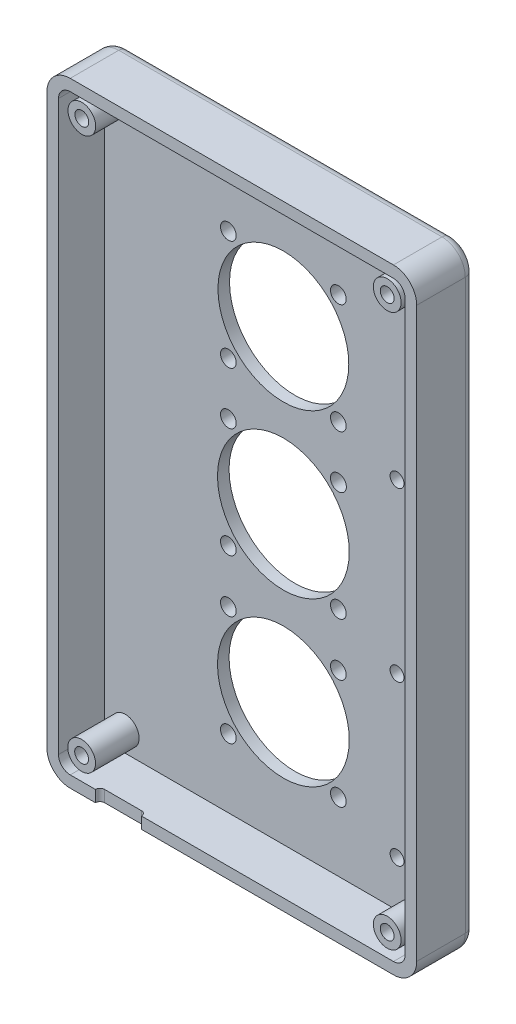
SolidWorks part; units mm, degrees
material "Plastique personnalisé"
ref_plane "Plan de face" through (0, 0, 0) normal (0, 0, 1) x (1, 0, 0)
ref_plane "Plan de dessus" through (0, 0, 0) normal (0, 1, 0) x (1, 0, 0)
ref_plane "Plan de droite" through (0, 0, 0) normal (1, 0, 0) x (0, 0, -1)
sketch "Esquisse1" plane through (0, 0, 0) normal (0, 0, 1) x (1, 0, 0)
  line L1 (-34.96, -64) -> (34.96, -64)
  line L2 (-37.5, -61.46) -> (-37.5, 61.46)
  line L3 (-34.96, 64) -> (34.96, 64)
  line L4 (37.5, -61.46) -> (37.5, 61.46)
  line L5 (-37.5, -64) -> (37.5, 64) construction
  line L6 (-37.5, 64) -> (37.5, -64) construction
  arc A0 (34.96, -64) -> (37.5, -61.46) centre (34.96, -61.46) ccw
  arc A1 (-34.96, -64) -> (-37.5, -61.46) centre (-34.96, -61.46) cw
  arc A2 (-37.5, 61.46) -> (-34.96, 64) centre (-34.96, 61.46) cw
  arc A3 (34.96, 64) -> (37.5, 61.46) centre (34.96, 61.46) cw
  point P0 (0, 0)
  dimension "D3" = 2.54
  dimension "D1" = 128
  dimension "D2" = 75
extrude "Boss.-Extru.1" add sketch "Esquisse1" along normal blind 10
shell "Coque1" thickness 2.5 removed face at (0, 0, 10) outward yes
fillet "Congé1" radius 2 8 edges at (40, 0, -2.5) (38.5238, -65.0238, -2.5) (0, -66.5, -2.5) (-38.5238, -65.0238, -2.5) (-40, 0, -2.5) (-38.5238, 65.0238, -2.5) (0, 66.5, -2.5) (38.5238, 65.0238, -2.5)
sketch "Esquisse3" plane through (0, 0, 0) normal (0, 0, 1) x (1, 0, 0)
  circle A0 centre (-33.02, 59.69) radius 1.5
  circle A1 centre (-33.02, 59.69) radius 3
  circle A2 centre (33.0465, 59.69) radius 1.5
  circle A3 centre (33.0465, 59.69) radius 3
  circle A4 centre (-33.06, -59.69) radius 3
  circle A5 centre (-33.06, -59.69) radius 1.5
  circle A6 centre (33.0465, -59.759) radius 3
  circle A7 centre (33.0465, -59.759) radius 1.5
  dimension "D1" = 3
  dimension "D2" = 3
extrude "Boss.-Extru.2" add sketch "Esquisse3" along normal up to surface (9.43 mm away)
sketch "Esquisse4" plane through (0, 0, 10) normal (0, 0, 1) x (1, 0, 0)
  line L0 (-24.5364, -63.3046) -> (-24.5364, -64) construction
  line L1 (-34.96, -64) -> (34.96, -64) construction
  line L2 (-24.5364, -64) -> (-24.5364, -64.0598) construction
  line L3 (-24.5364, -64.0598) -> (-24.5364, -66.5) construction
  line L4 (-34.96, -66.5) -> (34.96, -66.5) construction
  line L6 (-29.52, -66.5598) -> (-19.5528, -66.5598)
  line L7 (-29.52, -66.5598) -> (-29.52, -64)
  line L8 (-29.52, -64) -> (-19.5528, -64)
  line L9 (-19.5528, -66.5598) -> (-19.5528, -64)
  line L10 (-29.52, -66.5598) -> (-19.5528, -64) construction
  line L11 (-29.52, -64) -> (-19.5528, -66.5598) construction
  point P5 (-24.5364, -65.2799)
extrude "Enlèv. mat.-Extru.2" cut sketch "Esquisse4" against normal blind 1
fillet "Congé4" radius 1 2 edges at (-19.5528, -65.25, 9) (-29.52, -65.25, 9)
sketch "Esquisse5" plane through (0, 0, -2.5) normal (0, 0, -1) x (-1, 0, 0)
  circle A0 centre (-13.049, 44.9581) radius 1.7
  circle A1 centre (10.751, 44.9581) radius 1.7
  circle A2 centre (10.751, 21.1581) radius 1.7
  circle A3 centre (-13.049, 21.1581) radius 1.7
  circle A4 centre (-13.049, 9.7959) radius 1.7288
  circle A5 centre (10.751, 9.8247) radius 1.7
  circle A6 centre (10.751, -13.9753) radius 1.7
  circle A7 centre (-13.049, -13.9753) radius 1.7
  circle A8 centre (-13.049, -25.3963) radius 1.7
  circle A9 centre (10.751, -25.3963) radius 1.7
  circle A10 centre (10.751, -49.1963) radius 1.7
  circle A11 centre (-13.049, -49.1963) radius 1.7
  circle A12 centre (-1.149, -37.2963) radius 14.25
  circle A13 centre (-1.149, -2.0753) radius 14.25
  circle A14 centre (-1.149, 33.0581) radius 14.15
extrude "Enlèv. mat.-Extru.3" cut sketch "Esquisse5" against normal blind 10
sketch "Esquisse6" plane through (0, 0, 0) normal (0, 0, 1) x (1, 0, 0)
  circle A0 centre (25.7401, 16.6531) radius 1.5
  circle A1 centre (25.7401, -19.683) radius 1.5
  circle A2 centre (25.7401, -54.1208) radius 1.5
extrude "Enlèv. mat.-Extru.4" cut sketch "Esquisse6" against normal blind 10
